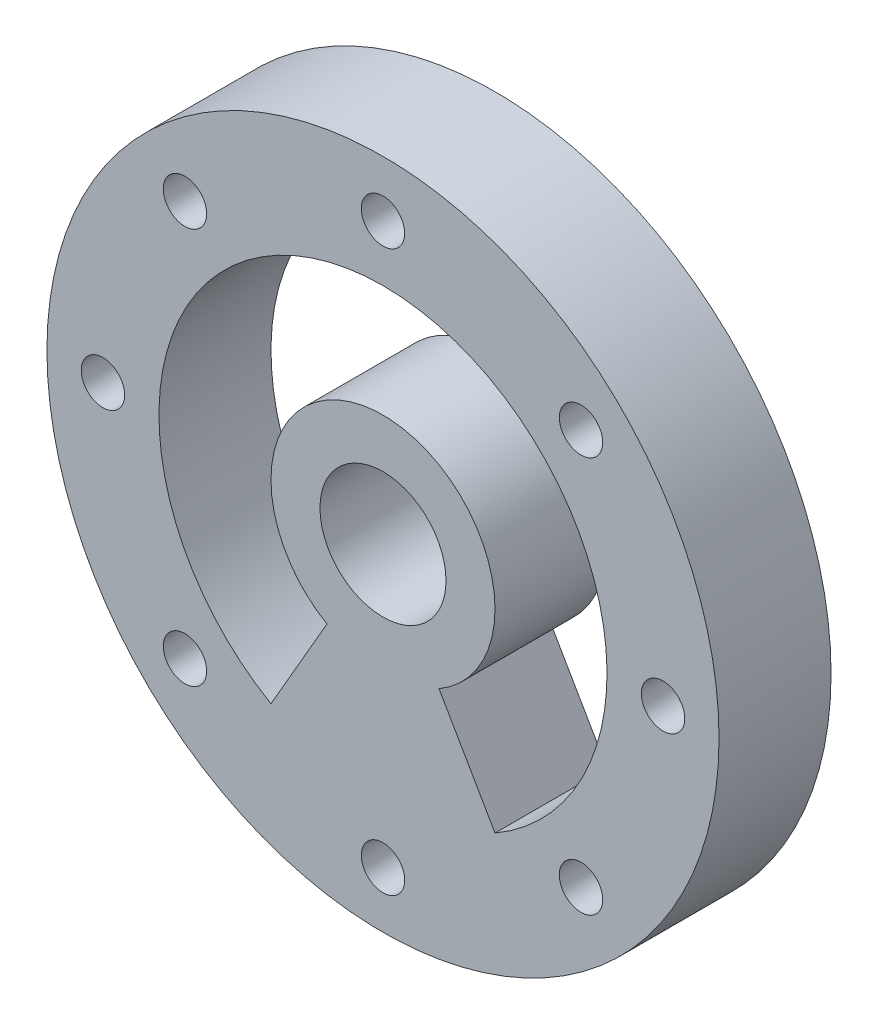
SolidWorks part; units mm, degrees
ref_plane "Front Plane" through (0, 0, 0) normal (0, 0, 1) x (1, 0, 0)
ref_plane "Top Plane" through (0, 0, 0) normal (0, 1, 0) x (1, 0, 0)
ref_plane "Right Plane" through (0, 0, 0) normal (1, 0, 0) x (0, 0, -1)
ref_axis "Axis1" through (0, 0, 5.5) along (0, 0, -1)
sketch "Sketch4" plane through (0, 0, 0) normal (0, 0, 1) x (1, 0, 0)
  line L0 (0, 0) -> (-9.5, -16.4545) construction
  line L1 (0, 0) -> (9.5, -16.4545) construction
  line L2 (-4, -6.9282) -> (-8, -13.8564)
  line L3 (4, -6.9282) -> (8, -13.8564)
  arc A1 (8, -13.8564) -> (-8, -13.8564) centre (0, 0) ccw
  arc A2 (4, -6.9282) -> (-4, -6.9282) centre (0, 0) ccw
sketch "Sketch6" plane through (0, 0, 0) normal (0, 0, 1) x (1, 0, 0)
  circle A0 centre (0, 0) radius 24
extrude "Boss-Extrude1" add sketch "Sketch6" along normal blind 8
extrude "Cut-Extrude4" cut sketch "Sketch4" along normal blind 8
sketch "Sketch7" plane through (0, 0, 0) normal (0, 0, -1) x (-1, 0, 0)
  circle A0 centre (0, 0) radius 4.5
extrude "Cut-Extrude5" cut sketch "Sketch7" against normal up to surface (8 mm away) up to face at (24, 0, 8)
sketch "Sketch8" plane through (0, 0, 8) normal (0, 0, -1) x (-1, 0, 0)
  line L0 (0, 0) -> (0, 20) construction
  circle A0 centre (0, 20) radius 1.55
  circle A1 centre (14.1421, 14.1421) radius 1.55
  circle A2 centre (20, 0) radius 1.55
  circle A3 centre (14.1421, -14.1421) radius 1.55
  circle A4 centre (0, -20) radius 1.55
  circle A5 centre (-14.1421, -14.1421) radius 1.55
  circle A6 centre (-20, 0) radius 1.55
  circle A7 centre (-14.1421, 14.1421) radius 1.55
  point P20 (0, 0)
  dimension "D1" = 8
extrude "Cut-Extrude6" cut sketch "Sketch8" along normal up to surface (8 mm away) up to face at (-4.5, 0, 0)
ref_plane "Plane1" through (0, 0, 4) normal (0, 0, 1) x (1, 0, 0)
